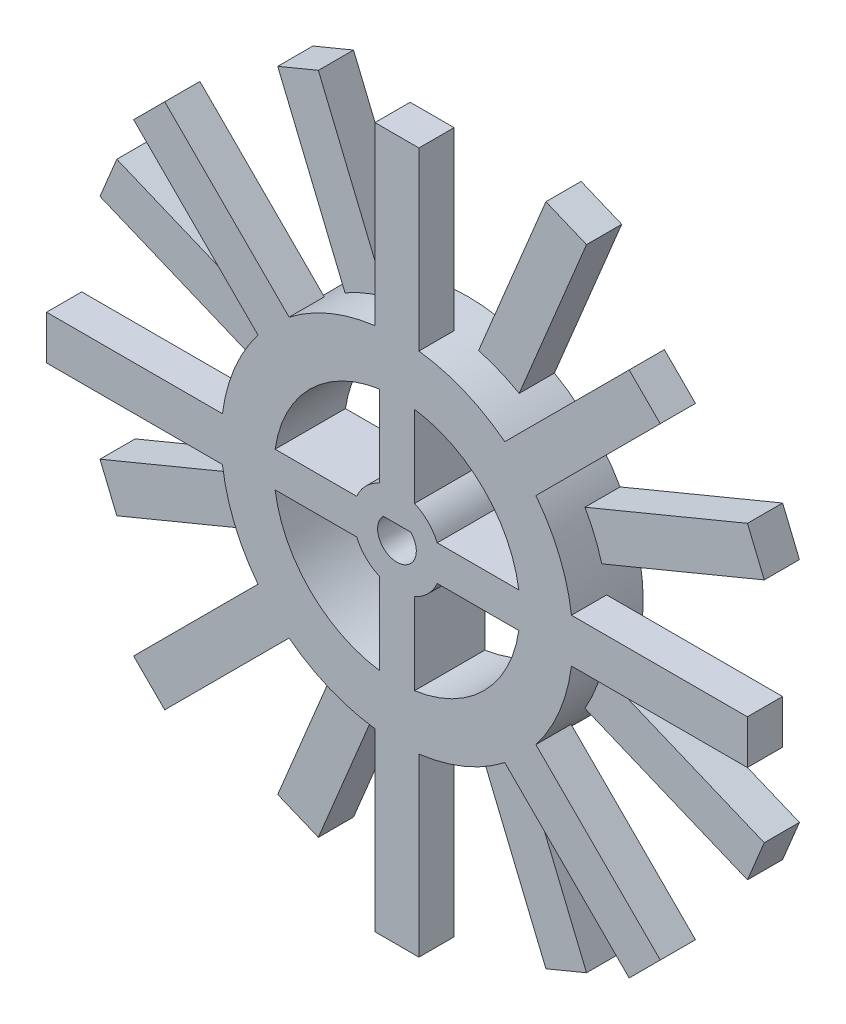
SolidWorks part; units mm, degrees
ref_plane "Спереди" through (0, 0, 0) normal (0, 0, 1) x (1, 0, 0)
ref_plane "Сверху" through (0, 0, 0) normal (0, 1, 0) x (1, 0, 0)
ref_plane "Справа" through (0, 0, 0) normal (1, 0, 0) x (0, 0, -1)
sketch "Эскиз2" plane through (0, 0, 0) normal (0, 0, 1) x (1, 0, 0)
  line L0 (-13.8564, 2) -> (-4.5826, 2)
  line L1 (0, 0) -> (-30, 0) construction
  line L2 (0, 0) -> (30, 0) construction
  line L3 (-13.8564, -2) -> (-4.5826, -2)
  line L4 (0, -20) -> (0, 1.55) construction
  line L5 (13.8564, -2) -> (4.5826, -2)
  line L6 (13.8564, 2) -> (4.5826, 2)
  line L7 (-2, 4.5826) -> (-2, 13.8564)
  line L8 (2, 4.5826) -> (2, 13.8564)
  line L9 (-2, -4.5826) -> (-2, -13.8564)
  line L10 (2, -4.5826) -> (2, -13.8564)
  line L11 (-1.5612, 1.55) -> (1.5612, 1.55)
  line L12 (0, 2.1) -> (0, 20) construction
  line L15 (-19.8431, -2.5) -> (-39.8431, -2.5)
  line L17 (-19.8431, 2.5) -> (-39.8431, 2.5)
  line L18 (-39.8431, 2.5) -> (-39.8431, -2.5)
  line L21 (-17.376, 9.9033) -> (-35.8535, 17.557)
  line L22 (-35.8535, 17.557) -> (-37.767, 12.9376)
  line L23 (-19.2894, 5.2839) -> (-37.767, 12.9376)
  line L24 (-12.2634, 15.799) -> (-26.4056, 29.9411)
  line L25 (-26.4056, 29.9411) -> (-29.9411, 26.4056)
  line L26 (-15.799, 12.2634) -> (-29.9411, 26.4056)
  line L27 (-5.2839, 19.2894) -> (-12.9376, 37.767)
  line L28 (-12.9376, 37.767) -> (-17.557, 35.8535)
  line L29 (-9.9033, 17.376) -> (-17.557, 35.8535)
  line L30 (2.5, 19.8431) -> (2.5, 39.8431)
  line L31 (2.5, 39.8431) -> (-2.5, 39.8431)
  line L32 (-2.5, 19.8431) -> (-2.5, 39.8431)
  line L33 (9.9033, 17.376) -> (17.557, 35.8535)
  line L34 (17.557, 35.8535) -> (12.9376, 37.767)
  line L35 (5.2839, 19.2894) -> (12.9376, 37.767)
  line L36 (15.799, 12.2634) -> (29.9411, 26.4056)
  line L37 (29.9411, 26.4056) -> (26.4056, 29.9411)
  line L38 (12.2634, 15.799) -> (26.4056, 29.9411)
  line L39 (19.2894, 5.2839) -> (37.767, 12.9376)
  line L40 (37.767, 12.9376) -> (35.8535, 17.557)
  line L41 (17.376, 9.9033) -> (35.8535, 17.557)
  line L42 (19.8431, -2.5) -> (39.8431, -2.5)
  line L43 (39.8431, -2.5) -> (39.8431, 2.5)
  line L44 (19.8431, 2.5) -> (39.8431, 2.5)
  line L45 (17.376, -9.9033) -> (35.8535, -17.557)
  line L46 (35.8535, -17.557) -> (37.767, -12.9376)
  line L47 (19.2894, -5.2839) -> (37.767, -12.9376)
  line L48 (12.2634, -15.799) -> (26.4056, -29.9411)
  line L49 (26.4056, -29.9411) -> (29.9411, -26.4056)
  line L50 (15.799, -12.2634) -> (29.9411, -26.4056)
  line L51 (5.2839, -19.2894) -> (12.9376, -37.767)
  line L52 (12.9376, -37.767) -> (17.557, -35.8535)
  line L53 (9.9033, -17.376) -> (17.557, -35.8535)
  line L54 (-2.5, -19.8431) -> (-2.5, -39.8431)
  line L55 (-2.5, -39.8431) -> (2.5, -39.8431)
  line L56 (2.5, -19.8431) -> (2.5, -39.8431)
  line L57 (-9.9033, -17.376) -> (-17.557, -35.8535)
  line L58 (-17.557, -35.8535) -> (-12.9376, -37.767)
  line L59 (-5.2839, -19.2894) -> (-12.9376, -37.767)
  line L60 (-15.799, -12.2634) -> (-29.9411, -26.4056)
  line L61 (-29.9411, -26.4056) -> (-26.4056, -29.9411)
  line L62 (-12.2634, -15.799) -> (-26.4056, -29.9411)
  line L63 (-19.2894, -5.2839) -> (-37.767, -12.9376)
  line L64 (-37.767, -12.9376) -> (-35.8535, -17.557)
  line L65 (-17.376, -9.9033) -> (-35.8535, -17.557)
  circle A1 centre (0, 0) radius 14
  circle A2 centre (0, 0) radius 5
  arc A3 (-1.5612, 1.55) -> (1.5612, 1.55) centre (0, 0) ccw
  circle A19 centre (0, 0) radius 20
  dimension "D1" = 28
  dimension "D2" = 40
  dimension "D3" = 10
  dimension "D5" = 30
  dimension "D8" = 4.4
  dimension "D4" = 2
  dimension "D6" = 30
  dimension "D7" = 2
  dimension "D9" = 1.55
  dimension "D10" = 20
  dimension "D11" = 2.5
  dimension "D12" = 16
extrude "Бобышка-Вытянуть3" add sketch "Эскиз2" along normal mid plane 8 contours A19
extrude "Вырез-Вытянуть6" cut sketch "Эскиз2<10>" against normal through all both and the other way through all contours A3 L11
sketch "Эскиз2<10>" plane through (0, 0, 0) normal (0, 0, 1) x (1, 0, 0) same geometry as "Эскиз2"
extrude "Вырез-Вытянуть7" cut sketch "Эскиз2<11>" against normal through all both and the other way through all contours A2 L6 A1 L8 | A2 L7 A1 L0 | A2 L3 A1 L9 | A2 L10 A1 L5 region at (-6.9806, 6.9806, 0) region at (-6.9806, -6.9806, 0) region at (6.9806, 6.9806, 0) region at (6.9806, -6.9806, 0)
sketch "Эскиз2<11>" plane through (0, 0, 0) normal (0, 0, 1) x (1, 0, 0) same geometry as "Эскиз2"
extrude "Бобышка-Вытянуть4" add sketch "Эскиз2<12>" along normal blind 4 contours A19 L42 L43 L44 | A19 L36 L37 L38 | A19 L30 L31 L32 | A19 L24 L25 L26 | A19 L17 L18 L15 | A19 L60 L61 L62 | A19 L54 L55 L56 | A19 L48 L49 L50 region at (-29.8954, 0, 0) region at (-21.1392, -21.1392, 0) region at (-21.1392, 21.1392, 0) region at (0, -29.8954, 0) region at (0, 29.8954, 0) region at (21.1392, -21.1392, 0) region at (21.1392, 21.1392, 0) region at (29.8954, 0, 0)
sketch "Эскиз2<12>" plane through (0, 0, 0) normal (0, 0, 1) x (1, 0, 0) same geometry as "Эскиз2"
extrude "Бобышка-Вытянуть5" add sketch "Эскиз2<13>" against normal blind 4 contours A19 L27 L28 L29 | A19 L21 L22 L23 | A19 L63 L64 L65 | A19 L57 L58 L59 | A19 L51 L52 L53 | A19 L45 L46 L47 | A19 L39 L40 L41 | A19 L33 L34 L35 region at (-27.6198, -11.4405, 0) region at (-27.6198, 11.4405, 0) region at (-11.4405, -27.6198, 0) region at (-11.4405, 27.6198, 0) region at (11.4405, -27.6198, 0) region at (11.4405, 27.6198, 0) region at (27.6198, -11.4405, 0) region at (27.6198, 11.4405, 0)
sketch "Эскиз2<13>" plane through (0, 0, 0) normal (0, 0, 1) x (1, 0, 0) same geometry as "Эскиз2"
